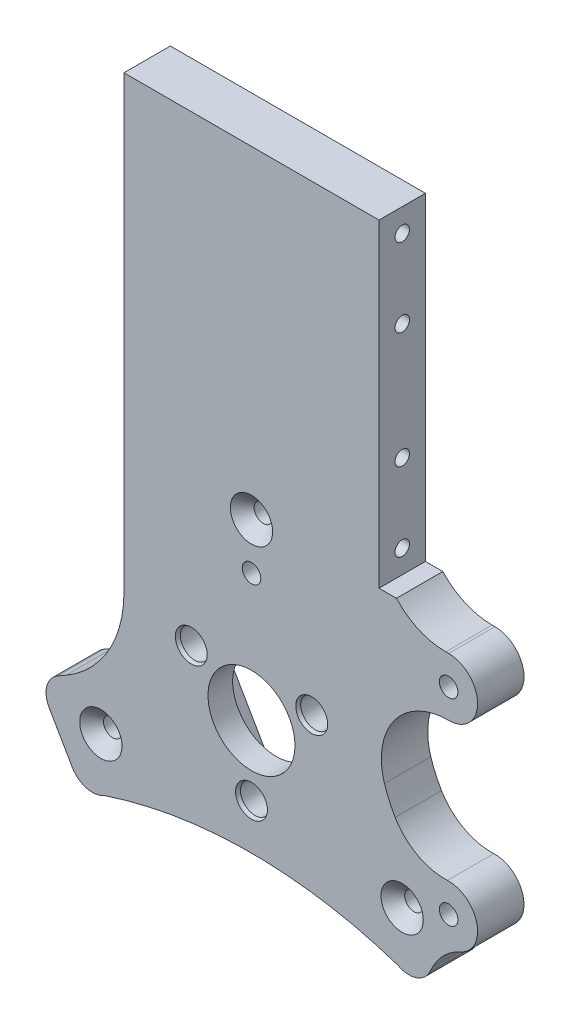
SolidWorks part; units mm, degrees
ref_plane "Front Plane" through (0, 0, 0) normal (0, 0, 1) x (1, 0, 0)
ref_plane "Top Plane" through (0, 0, 0) normal (0, 1, 0) x (1, 0, 0)
ref_plane "Right Plane" through (0, 0, 0) normal (1, 0, 0) x (0, 0, -1)
sketch "Sketch1" plane through (0, 0, 0) normal (0, 0, 1) x (1, 0, 0)
  line L0 (-1000, 0) -> (49000, 0) construction
  line L1 (0, -1000) -> (0, 49000) construction
  line L2 (0, 0) -> (-37.6779, -21.7533) construction
  line L3 (0, 0) -> (34.4865, -19.9108) construction
  line L4 (10, -8.7457) -> (10, 8.7457) construction
  line L5 (10.3863, 10.4956) -> (-10.3863, 10.4956)
  line L6 (-14.2847, 3.7444) -> (-3.9035, -14.2421)
  line L7 (3.9036, -14.242) -> (14.2846, 3.7447)
  line L8 (9.0941, -5.2486) -> (-10.3863, 5.9944) construction
  line L9 (0, -11.9891) -> (0, 10.4956) construction
  line L10 (10.3863, 5.9946) -> (-9.0941, -5.2488) construction
  line L11 (-30.909, -22.4641) -> (-34.909, -15.5359)
  line L12 (-32, -9.2376) -> (-33.4449, -10.0718)
  line L13 (-25, -23.6714) -> (-25.4449, -23.9282)
  line L14 (24.7944, -23.6821) -> (25.2453, -23.9282)
  line L15 (30.7512, -22.1827) -> (34.3345, -14.8973)
  line L16 (22, 49.7573) -> (-22, 49.7573)
  line L17 (22, 49.7573) -> (22, 38.5054)
  line L18 (32, -9.2376) -> (32.7451, -9.6678)
  line L19 (-22, 49.7573) -> (-22, 8.0829)
  line L20 (-4, 6.9282) -> (-41.6779, -14.8251) construction
  line L21 (34, 27.0109) -> (33.4945, 27.0109)
  line L22 (34, 17.0109) -> (33.8909, 17.0109)
  line L25 (-12, 0) -> (-12.0927, -0.0535)
  circle A0 centre (0, 0) radius 30 construction
  circle A1 centre (0, 0) radius 7.5
  circle A2 centre (0, 30) radius 4 construction
  circle A3 centre (25.9808, -15) radius 4 construction
  circle A4 centre (-25.9808, -15) radius 4 construction
  arc A5 (-10.3863, 10.4956) -> (-14.2847, 3.7444) centre (-10.3863, 5.9944) ccw
  arc A6 (-3.9035, -14.2421) -> (3.9036, -14.242) centre (0, -11.9891) ccw
  arc A7 (14.2846, 3.7447) -> (10.3863, 10.4956) centre (10.3863, 5.9946) ccw
  circle A8 centre (27.3746, 42.204) radius 2.5
  circle A9 centre (-27.6254, 42.204) radius 2.5
  arc A10 (32, -9.2376) -> (22.9322, 2.0481) centre (42, 8.0829) cw
  arc A11 (-22, 8.0829) -> (-32, -9.2376) centre (-42, 8.0829) cw
  arc A12 (25.2453, -23.9282) -> (-25.4449, -23.9282) centre (-0.0998, -99.8072) ccw
  arc A13 (30.7512, -22.1827) -> (25.2453, -23.9282) centre (27.1619, -20.4173) cw
  arc A14 (32.7451, -9.6678) -> (34.3345, -14.8973) centre (30.7451, -13.1319) cw
  arc A15 (-30.909, -22.4641) -> (-25.4449, -23.9282) centre (-27.4449, -20.4641) ccw
  arc A16 (-33.4449, -10.0718) -> (-34.909, -15.5359) centre (-31.4449, -13.5359) ccw
  circle A17 centre (34, -11.9891) radius 5
  arc A18 (34, 17.0109) -> (34, 27.0109) centre (34, 22.0109) ccw
  arc A19 (22, 38.5054) -> (33.4945, 27.0109) centre (33.4945, 38.5054) ccw
  arc A20 (33.8909, 17.0109) -> (22.9322, 2.0481) centre (33.8909, 5.5165) ccw
  point P4 (0, 0)
  point P19 (0, 0)
  point P21 (10, 0)
  point P40 (0, 0.9917)
  point P46 (0, 49.7573)
  point P47 (-32.909, -19)
  point P62 (28.909, -25.9282)
  point P67 (-28.909, -25.9282)
  line B0 (37, -11.9891) -> (-75, -11.9891) construction
  line B1 (0, -11.9891) -> (0, 22.0109) construction
  line B2 (-14.25, -36.1891) -> (-14.25, -11.9891) construction
  line B3 (-29.75, -13.311) -> (-29.75, -10.6672) construction
  line B4 (-39.75, -13.2558) -> (-39.75, -10.7223) construction
  line B5 (34, -11.9891) -> (34, 22.0109) construction
  line B6 (37, 27.0109) -> (37, -16.9891) construction
  line B7 (37, 27.0109) -> (-3, 27.0109) construction
  line B8 (37, -16.9891) -> (-3, -16.9891) construction
  line B9 (-14.25, -11.9891) -> (-14.25, 75.8256) construction
  line B10 (-3, 27.0109) -> (-3, -16.9891) construction
  dimension "D1" = 60
  dimension "D4" = 15
  dimension "D5" = 3
  dimension "D7" = 55
  dimension "D9" = 8
  dimension "D11" = 20
  dimension "D12" = 11.4945
  dimension "D13" = 4
  dimension "D14" = 4
  dimension "D15" = 11.4945
  dimension "D2" = 120
  dimension "D3" = 120
  dimension "D6" = 10
  dimension "D8" = 44
  dimension "D10" = 8
sketch_block_instance "HemeraFrontContraints-3"
sketch_block "HemeraFrontContraints" parameters "D1"=34, "D2"=48.25, "D3"=63.75, "D4"=73.75, "D5"=24.2, "D6"=34, "D7"=34, "D8"=31.699, "D9"=36.9763, "D10"=44
sketch "Sketch2" plane through (0, 0, 0) normal (0, 1, 0) x (1, 0, 0)
  line L0 (52, -10) -> (52, -104) construction
  line L1 (-49, 0) -> (49, 0) construction
  line L2 (-52, -10) -> (-52, -104) construction
  line L3 (-52, -104) -> (52, -104) construction
  line L4 (0, 0) -> (0, -30) construction
  line L7 (-52, -10) -> (-49, -10) construction
  line L8 (-49, 0) -> (-49, -10) construction
  line L11 (52, -10) -> (49, -10) construction
  line L12 (49, 0) -> (49, -10) construction
  point P12 (0, -104)
  dimension "D1" = 98
  dimension "D2" = 104
  dimension "D3" = 30
  dimension "D4" = 10
  dimension "D7" = 104
extrude "Boss-Extrude1" add sketch "Sketch1" along normal blind 8 contours A7 L7 A6 L6 A5 L5 | L17 | L19 | L16 L19 L17 | A10 A17 L15 A14 L18 | L15 A17 A10 L18 A14 region at (1.5486, 13.9173, 0) region at (31.8342, -12.7141, 0) region at (35.6729, -11.4291, 0)
extrude "Boss-Extrude2" add sketch "Sketch1<3>" along normal blind 4.25 from offset 3.75 contours L7 A7 L5 A5 L6 A6 A1 region at (13.936, 8.0445, 0)
sketch "Sketch1<3>" plane through (0, 0, 0) normal (0, 0, 1) x (1, 0, 0) same geometry as "Sketch1"
sketch "Sketch15" plane through (0, 49.7573, 0) normal (0, 1, 0) x (1, 0, 0)
  line L4 (22, 0) -> (-22, 0)
  line L5 (-22, 0) -> (-22, -8)
  line L6 (-22, -8) -> (22, -8)
  line L7 (22, -8) -> (22, 0)
  line L8 (22, 0) -> (-22, 0)
  line L9 (-22, 0) -> (-22, -8)
  line L10 (-22, -8) -> (22, -8)
  line L11 (22, -8) -> (22, 0)
  dimension "D1" = 0
extrude "Boss-Extrude3" add sketch "Sketch15" along normal blind 36
sketch "Sketch4" plane through (0, 0, 0) normal (0, 0, -1) x (-1, 0, 0)
  line L0 (0, 26) -> (0, 34)
  arc A0 (0, 26) -> (0, 34) centre (0, 30) ccw
revolve "Cut-Revolve1" cut sketch "Sketch4" angle 360 about L0
sketch "Sketch22" plane through (0, 0, 8) normal (0, 0, 1) x (1, 0, 0)
  line L0 (22, 49.7573) -> (22, 38.5054) construction
  line L1 (22, 40.7573) -> (27, 40.7573)
  line L2 (22, 40.7573) -> (22, 30.7573)
  line L3 (22, 30.7573) -> (27, 30.7573)
  line L4 (27, 40.7573) -> (27, 30.7573)
  dimension "D1" = 10
  dimension "D2" = 5
  dimension "D3" = 30.7573
extrude "Cut-Extrude1" cut sketch "Sketch22" against normal blind 10
sketch "Sketch5" plane through (0, 0, 0) normal (0, 0, -1) x (-1, 0, 0)
  line L0 (-22.5167, -13) -> (-29.4449, -17)
  line L1 (0, 0) -> (-34.4865, -19.9108) construction
  arc A0 (-22.5167, -13) -> (-29.4449, -17) centre (-25.9808, -15) ccw
revolve "Cut-Revolve2" cut sketch "Sketch5" angle 360 about L0
sketch "Sketch6" plane through (0, 0, 0) normal (0, 0, -1) x (-1, 0, 0)
  line L0 (22.5167, -13) -> (29.4449, -17)
  line L1 (0, 0) -> (37.6779, -21.7533) construction
  arc A0 (22.5167, -13) -> (29.4449, -17) centre (25.9808, -15) ccw
revolve "Cut-Revolve3" cut sketch "Sketch6" angle 360 about L0
hole_wizard "CSK for M3 Flat Head Machine Screw1" positions "Sketch7" profile "Sketch8" countersink size "M3" standard "ANSI Metric" end condition through all
sketch "Sketch7" plane through (0, 0, 8) normal (0, 0, 1) x (1, 0, 0)
  point P0 (0, 30)
  point P3 (25.9808, -15)
  point P6 (-25.9808, -15)
sketch "Sketch8" plane through (0, 30, 8) normal (1, 0, 0) x (0, -1, 0)
  line L0 (0, 0) -> (0, 8)
  line L1 (0, 8) -> (1.6, 8)
  line L2 (1.6, 8) -> (1.6, 2.05)
  line L3 (1.6, 2.05) -> (3.65, 0)
  line L5 (3.65, 0) -> (0, 0)
  line L6 (-1.6, 2.05) -> (-3.65, 0) construction
  line L11 (0, -6.35) -> (0, 107.95) construction
  dimension "Thru Hole Dia." = 3.2
  dimension "Thru Hole Depth" = 8
  dimension "Near C'Sink Dia." = 7.3
  dimension "Near C'Sink Angle" = 90
hole_wizard "CBORE for M3 SBHCS2" positions "Sketch11" profile "Sketch12" counterbore size "M3" standard "ANSI Metric" end condition through all
sketch "Sketch11" plane through (0, 0, 0) normal (0, 0, -1) x (-1, 0, 0)
  point P0 (-34, 22.0109)
  point P3 (0, 22.0109)
  point P6 (0, -11.9891)
  point P19 (-34, -11.9891)
sketch "Sketch12" plane through (34, 22.0109, 0) normal (1, 0, 0) x (0, 1, 0)
  line L0 (0, 0) -> (0, 8)
  line L1 (0, 8) -> (1.6, 8)
  line L3 (1.6, 8) -> (1.6, 3)
  line L4 (3.35, 3) -> (1.6, 3)
  line L5 (3.35, 3) -> (3.35, 0.025)
  line L6 (3.35, 0.025) -> (3.375, 0)
  line L7 (3.375, 0) -> (0, 0)
  line L8 (-3.35, 0.025) -> (-3.375, 0) construction
  line L11 (0, -6.35) -> (0, 107.95) construction
  dimension "Thru Hole Dia." = 3.2
  dimension "Thru Hole Depth" = 8
  dimension "C'Bore Dia." = 6.7
  dimension "C'Bore Depth" = 3
  dimension "Near C'Sink Dia." = 6.75
  dimension "Near C'Sink Angle" = 90
hole_wizard "CSK for M4 Flat Head Machine Screw1" positions "Sketch13" profile "Sketch14" countersink size "M4" standard "ANSI Metric" end condition through all
sketch "Sketch13" plane through (0, 0, 8) normal (0, 0, 1) x (1, 0, 0)
  point P0 (-10.3863, 5.9944)
  point P3 (10.3863, 5.9946)
  point P6 (0, -11.9891)
sketch "Sketch14" plane through (-10.3863, 5.9944, 8) normal (1, 0, 0) x (0, -1, 0)
  line L0 (0, 0) -> (0, 8)
  line L1 (0, 8) -> (2.5, 8)
  line L2 (2.5, 8) -> (2.5, 0.6036)
  line L3 (2.5, 0.6036) -> (2.75, 0)
  line L5 (2.75, 0) -> (0, 0)
  line L6 (-2.5, 0.6036) -> (-2.75, 0) construction
  line L11 (0, -6.35) -> (0, 107.95) construction
  dimension "Thru Hole Dia." = 5
  dimension "Thru Hole Depth" = 8
  dimension "Near C'Sink Dia." = 5.5
  dimension "Near C'Sink Angle" = 45
fillet "Fillet1" radius 10 2 edges at (30.5834, -8.3385, 4) (33.328, -16.9437, 4)
hole_wizard "Tap Drill for M3x0.5 Tap4" positions "Sketch25" profile "Sketch26" hole size "M3x0.5" standard "ANSI Metric"
sketch "Sketch25" plane through (22, 0, 0) normal (1, 0, 0) x (0, 0, -1)
  line L0 (-8, 85.7573) -> (0, 85.7573) construction
  line L1 (0, 85.7573) -> (0, 30.7573) construction
  point P0 (-4, 81.7573)
  point P2 (-4, 68.2573)
  point P4 (-4, 34.7573)
  point P6 (-4, 48.2573)
  dimension "D1" = 4
  dimension "D2" = 13.5
  dimension "D3" = 13.5
  dimension "D4" = 20
  dimension "D5" = 4
sketch "Sketch26" plane through (22, 81.7573, 4) normal (0, 1, 0) x (0, 0, -1)
  line L0 (0, 0) -> (0, 5.7511)
  line L1 (0, 5.7511) -> (1.25, 5)
  line L2 (1.25, 5) -> (1.25, 0)
  line L5 (1.25, 0) -> (0, 0)
  line L10 (0, 5.7511) -> (-1.25, 5) construction
  line L11 (0, -6.35) -> (0, 107.95) construction
  dimension "Hole Dia." = 2.5
  dimension "Hole Depth" = 5
  dimension "Drill Angle" = 118
mirror "Mirror1" about plane through (0, 0, 0) normal (1, 0, 0) of "Tap Drill for M3x0.5 Tap4"
sketch "Sketch27" plane through (0, 0, 0) normal (0, 0, -1) x (-1, 0, 0)
  line L0 (-22, 70.5898) -> (22, 70.5898) construction
  line L1 (-22, 85.7573) -> (-22, 30.7573) construction
  line L2 (22, 85.7573) -> (22, 8.0829) construction
  text T0 "HEMERA" font "Century Gothic" height 7.5
extrude "Cut-Extrude2" cut sketch "Sketch27" against normal blind 1
